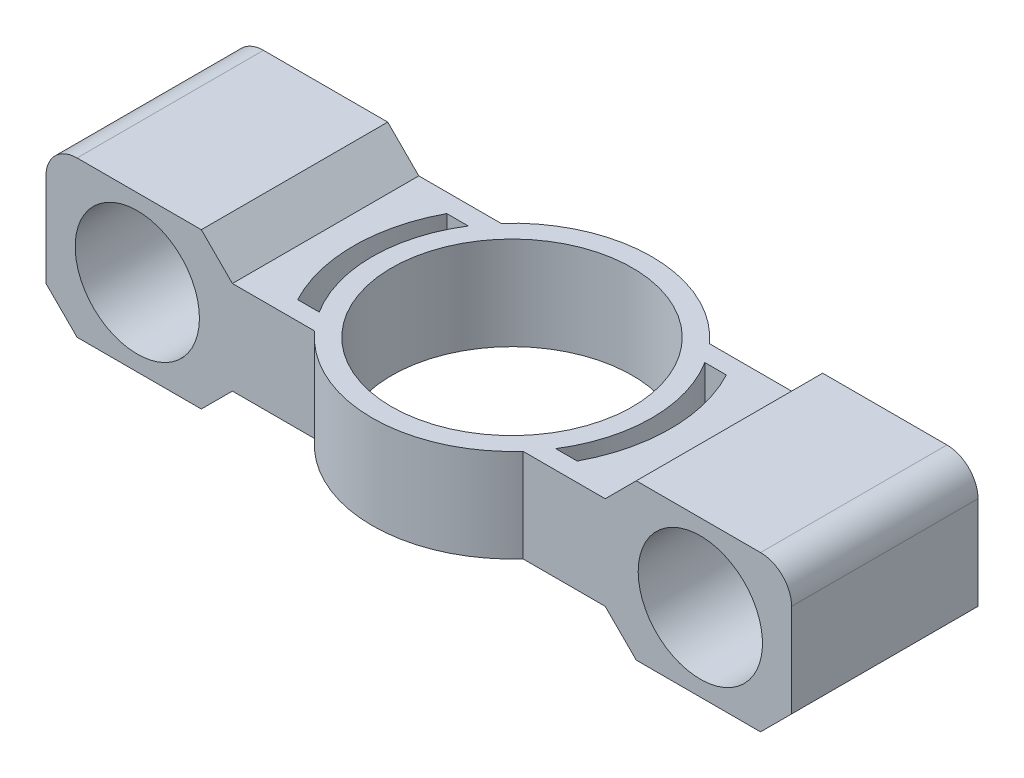
SolidWorks part; units mm, degrees
ref_plane "Front Plane" through (0, 0, 0) normal (0, 0, 1) x (1, 0, 0)
ref_plane "Top Plane" through (0, 0, 0) normal (0, 1, 0) x (1, 0, 0)
ref_plane "Right Plane" through (0, 0, 0) normal (1, 0, 0) x (0, 0, -1)
sketch "Sketch1" plane through (0, 0, 0) normal (0, 1, 0) x (1, 0, 0)
  line L0 (36, 18) -> (36, -18)
  line L1 (-72, -18) -> (-20.1246, -18)
  line L2 (-72, -18) -> (-72, 18)
  line L3 (-72, 18) -> (-20.1246, 18)
  line L4 (72, -18) -> (72, 18)
  line L5 (0, 33.4543) -> (0, 0) construction
  line L6 (-36, 18) -> (-36, -18)
  line L7 (22.8394, 14.4) -> (27, 14.4)
  line L10 (-27, 14.4) -> (-22.8394, 14.4)
  line L11 (-27, -14.4) -> (-22.8394, -14.4)
  line L12 (22.8394, -14.4) -> (27, -14.4)
  line L14 (20.1246, -18) -> (72, -18)
  line L15 (20.1246, 18) -> (72, 18)
  circle A0 centre (0, 0) radius 16.5
  circle A1 centre (0, 0) radius 23.25
  arc A2 (-20.1246, -18) -> (20.1246, -18) centre (0, 0) ccw
  arc A3 (-27, 14.4) -> (-27, -14.4) centre (0, 0) ccw
  arc A4 (27, -14.4) -> (27, 14.4) centre (0, 0) ccw
  arc A5 (22.8394, -14.4) -> (22.8394, 14.4) centre (0, 0) ccw
  arc A6 (20.1246, 18) -> (-20.1246, 18) centre (0, 0) ccw
  arc A7 (-22.8394, 14.4) -> (-22.8394, -14.4) centre (0, 0) ccw
  point P16 (0, 0)
  dimension "D1" = 33
  dimension "D2" = 46.5
  dimension "D3" = 54
  dimension "D4" = 51.8754
  dimension "D9" = 51.8754
  dimension "D16" = 14.4
  dimension "D5" = 36
  dimension "D6" = 36
  dimension "D7" = 51.8754
  dimension "D10" = 36
  dimension "D11" = 4.1606
  dimension "D12" = 27
  dimension "D13" = 28.8
  dimension "D14" = 54
  dimension "D15" = 30.6
  dimension "D17" = 4.1606
extrude "Boss-Extrude3" add sketch "Sketch1" along normal mid plane 30 contours L6 L3 L2 L1 | L15 L0 L14 L4 region at (54, 0, 0) region at (-54, 0, 0)
extrude "Boss-Extrude4" add sketch "Sketch1<6>" along normal mid plane 18 contours L15 A6 A1 L3 L6 L1 A2 L14 L0 L12 A5 L7 A4 L10 A7 L11 A3 region at (35.1, 0, 0)
sketch "Sketch1<6>" plane through (0, 0, 0) normal (0, 1, 0) x (1, 0, 0) same geometry as "Sketch1"
chamfer "Chamfer3" distance 6 angle 45 6 edges at (36, 15, 0) (72, -15, 0) (36, -15, 0) (-36, -15, 0) (-72, -15, 0) (-36, 15, 0)
fillet "Fillet1" radius 6 2 edges at (72, 15, 0) (-72, 15, 0)
sketch "Sketch2" plane through (0, 0, 18) normal (0, 0, 1) x (1, 0, 0)
  line L0 (0, 0) -> (0, 28.6074) construction
  circle A0 centre (-54.3699, 0) radius 12
  circle A1 centre (-54.3699, 0) radius 6.5
  circle A2 centre (54.3699, 0) radius 6.5
  circle A3 centre (54.3699, 0) radius 12
  dimension "D1" = 24
  dimension "D2" = 13
extrude "Cut-Extrude2" cut sketch "Sketch2" against normal blind 64.5 contours A1 | A2 region at (-54.3699, 0, 18) region at (54.3699, 0, 18)
extrude "Cut-Extrude3" cut sketch "Sketch2<4>" against normal blind 19.5
sketch "Sketch2<4>" plane through (0, 0, 18) normal (0, 0, 1) x (1, 0, 0) same geometry as "Sketch2"
sketch "Sketch4" plane through (0, 0, -1.5) normal (0, 0, 1) x (1, 0, 0)
  line L0 (0, 0) -> (0, 29.9772) construction
  circle A0 centre (54.3699, 0) radius 12
  circle A1 centre (54.3699, 0) radius 6.5
  circle A2 centre (-54.3699, 0) radius 12
  circle A3 centre (-54.3699, 0) radius 6.5
extrude "Cut-Extrude5" cut sketch "Sketch4" against normal offset from surface (87 mm away) 94.5 from offset 7.5 up to face at (-47.8699, 0, -1.5) offset against normal yes
